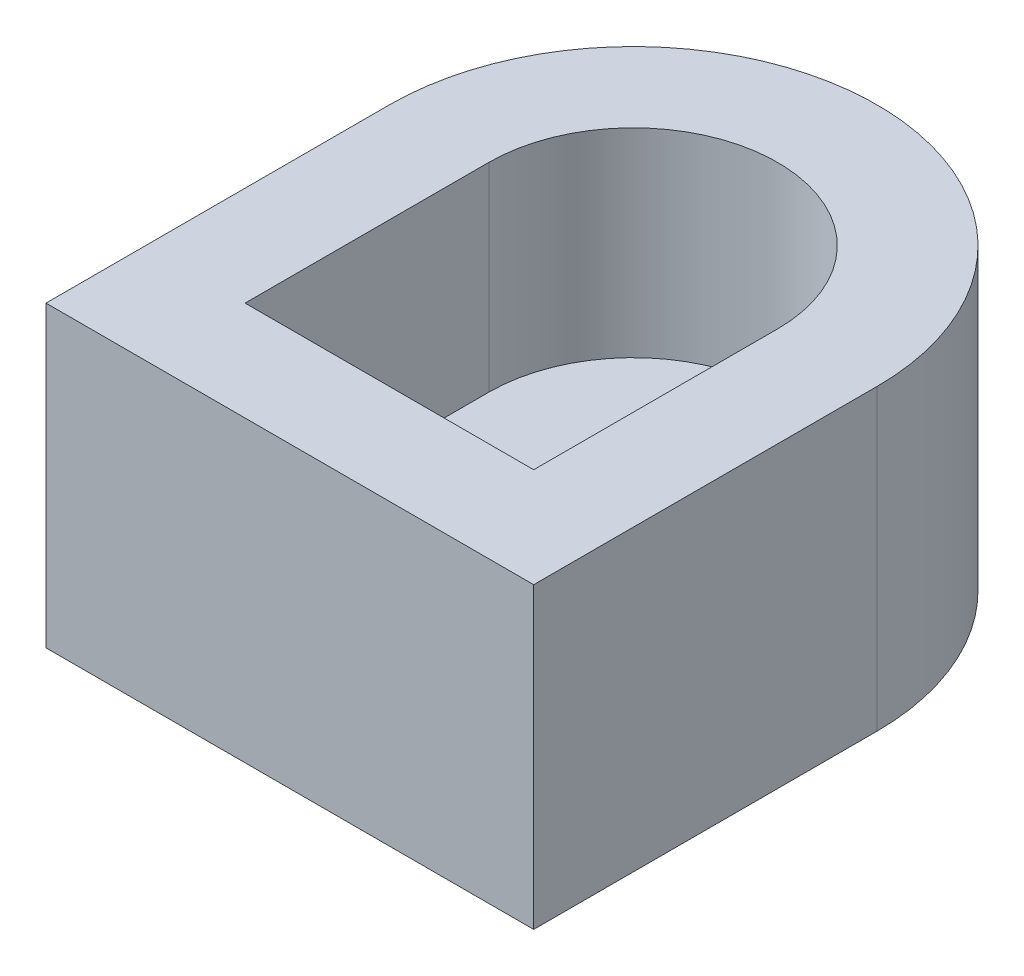
SolidWorks part; units mm, degrees
ref_plane "Front Plane" through (0, 0, 0) normal (0, 0, 1) x (1, 0, 0)
ref_plane "Top Plane" through (0, 0, 0) normal (0, 1, 0) x (1, 0, 0)
ref_plane "Right Plane" through (0, 0, 0) normal (1, 0, 0) x (0, 0, -1)
sketch "Sketch1" plane through (0, 0, 0) normal (0, 1, 0) x (1, 0, 0)
  line L0 (-4.9, -4.9) -> (-2.9, -4.9) construction
  line L1 (-2.9, 0) -> (2.9, 0)
  line L2 (-2.9, 0) -> (-2.9, -4.9)
  line L3 (-2.9, -4.9) -> (2.9, -4.9)
  line L4 (2.9, 0) -> (2.9, -4.9)
  line L5 (-4.9, 0) -> (4.9, 0)
  line L6 (-4.9, 0) -> (-4.9, -6.9)
  line L7 (-4.9, -6.9) -> (4.9, -6.9)
  line L8 (4.9, 0) -> (4.9, -6.9)
  line L10 (-2.9, -4.9) -> (-2.9, -6.9) construction
  circle A0 centre (0, 0) radius 2.9
  circle A1 centre (0, 0) radius 4.9
  point P13 (-2.8264, -4.9)
  point P14 (6.606, -9.0726)
  point P17 (0, 0)
  point P18 (0, 0)
  point P19 (-2.9, -4.9779)
  dimension "D1" = 5.8
  dimension "D2" = 2
  dimension "D3" = 4.9
extrude "Boss-Extrude1" add sketch "Sketch1" along normal blind 4 contours L5 A1 A0 | L5 A1 L2 | A1 L4 L3 L2 L6 L7 L8 | L4 A1 L5 region at (-3.7159, 0, 1.5318) region at (-3.9, 0, -0.1096) region at (3.7159, 0, 1.5318) region at (0, 0, 5.2131)
extrude "Boss-Extrude2" add sketch "Sketch1<3>" against normal blind 2 contours A1 L4 L3 L2 L6 L7 L8 | A1 L2 L3 | A1 L3 L4 | A1 L4 A0 L2 | L4 A1 L5 | L5 A1 L2 | L5 A1 A0 | L1 A0 | L1 A0 region at (0, 0, -1.2308) region at (0, 0, 3.3636) region at (-3.7159, 0, 1.5318) region at (-3.9, 0, -0.1096) region at (0, 0, 1.2308) region at (3.7159, 0, 1.5318) region at (-2.1898, 0, 4.6204) region at (0, 0, 5.2131) region at (2.1898, 0, 4.6204)
sketch "Sketch1<3>" plane through (0, 0, 0) normal (0, 1, 0) x (1, 0, 0) same geometry as "Sketch1"
